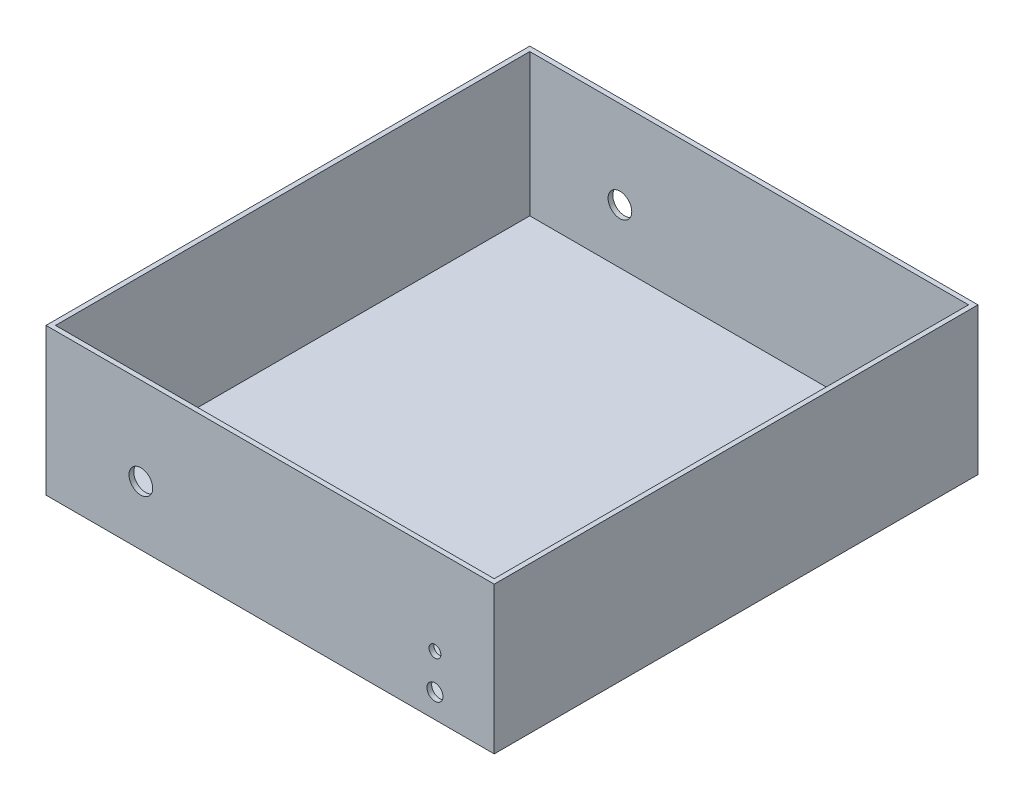
SolidWorks part; units mm, degrees
material "ABS"
ref_plane "Front Plane" through (0, 0, 0) normal (0, 0, 1) x (1, 0, 0)
ref_plane "Top Plane" through (0, 0, 0) normal (0, 1, 0) x (1, 0, 0)
ref_plane "Right Plane" through (0, 0, 0) normal (1, 0, 0) x (0, 0, -1)
sketch "Sketch2" plane through (0, 0, 0) normal (0, 1, 0) x (1, 0, 0)
  line L0 (-94.5, 102) -> (-94.5, -102)
  line L1 (-92.5, 100) -> (92.5, 100)
  line L2 (-92.5, 100) -> (-92.5, -100)
  line L3 (-92.5, -100) -> (92.5, -100)
  line L4 (92.5, 100) -> (92.5, -100)
  line L5 (-92.5, 100) -> (92.5, -100) construction
  line L6 (-92.5, -100) -> (92.5, 100) construction
  line L7 (-94.5, -102) -> (94.5, -102)
  line L8 (94.5, 102) -> (94.5, -102)
  line L9 (-94.5, 102) -> (94.5, 102)
  point P0 (0, 0)
  dimension "D1" = 200
  dimension "D2" = 185
  dimension "D3" = 2
extrude "Walls" add sketch "Sketch2" along normal blind 60
sketch "Sketch3" plane through (0, 0, 0) normal (0, -1, 0) x (1, 0, 0)
  line L1 (-94.5, -102) -> (94.5, -102)
  line L2 (-94.5, -102) -> (-94.5, 102)
  line L3 (-94.5, 102) -> (94.5, 102)
  line L4 (94.5, -102) -> (94.5, 102)
  line L5 (-94.5, -102) -> (94.5, 102) construction
  line L6 (-94.5, 102) -> (94.5, -102) construction
  point P0 (0, 0)
extrude "Base" add sketch "Sketch3" along normal blind 2
sketch "Sketch4" plane through (0, 0, -102) normal (0, 0, -1) x (-1, 0, 0)
  line L1 (94.5, -2) -> (-94.5, -2) construction
  line L2 (-94.5, 60) -> (-94.5, -2) construction
  line L3 (94.5, 60) -> (94.5, -2) construction
  circle A0 centre (-69.5, 23) radius 2.5
  circle A1 centre (54.5, 23) radius 5
  point P4 (0, 0)
  dimension "D1" = 5
  dimension "D2" = 10
  dimension "D3" = 25
  dimension "D4" = 25
  dimension "D5" = 40
extrude "Cut-Extrude1" cut sketch "Sketch4" against normal through all
sketch "Sketch5" plane through (0, 0, -102) normal (0, 0, -1) x (-1, 0, 0)
  circle A0 centre (-69.5, 8.0963) radius 3.3782 construction
  circle A1 centre (-69.5, 8.0963) radius 3.3782
extrude "Cut-Extrude2" cut sketch "Sketch5" against normal through all
